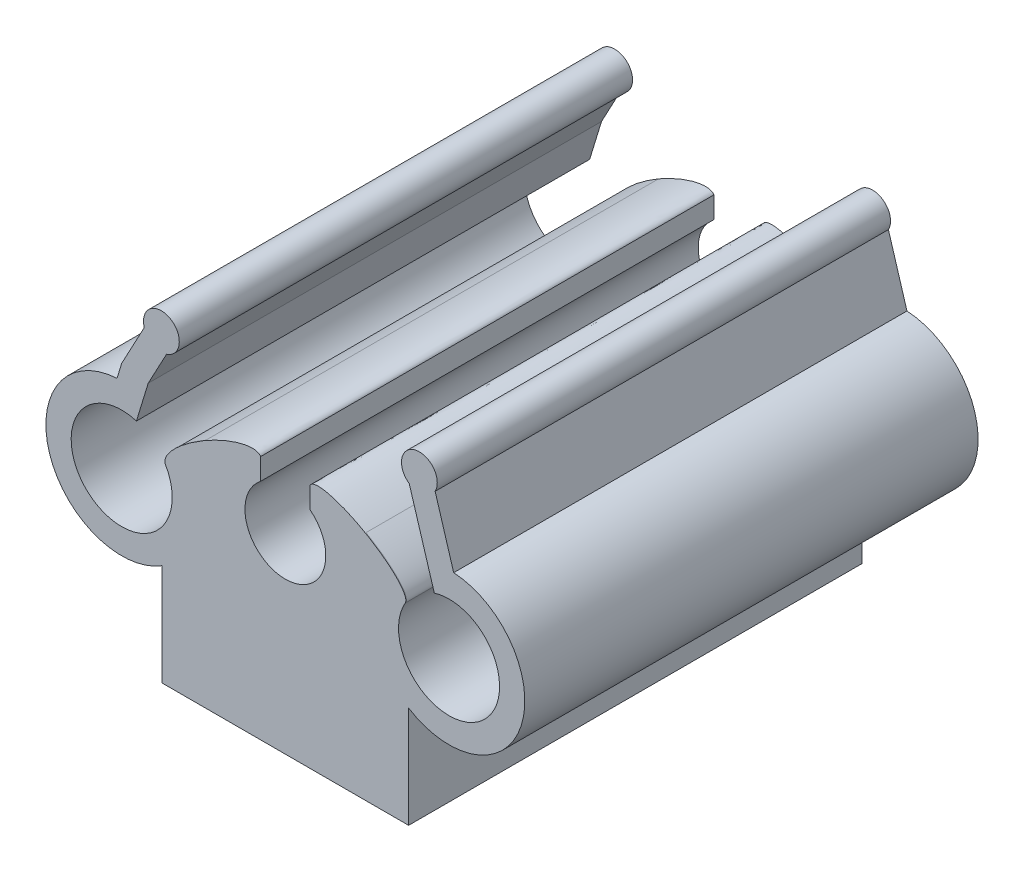
SolidWorks part; units mm, degrees
ref_plane "Ön Düzlem" through (0, 0, 0) normal (0, 0, 1) x (1, 0, 0)
ref_plane "Üst Düzlem" through (0, 0, 0) normal (0, 1, 0) x (1, 0, 0)
ref_plane "Sağ Düzlem" through (0, 0, 0) normal (1, 0, 0) x (0, 0, -1)
sketch "Çizim1" plane through (0, 0, 0) normal (0, 0, 1) x (1, 0, 0)
  line L0 (0, 0) -> (12.2, 0)
  line L1 (12.2, 0) -> (12.2, 4.1689)
  line L3 (0, 4.1689) -> (0, 0)
  line L4 (-2, 12.7) -> (-1.3113, 14.9713)
  line L5 (5.1136, 12.2788) -> (5.1136, 10.9455)
  line L6 (-0.1151, 14.6086) -> (-0.7477, 12.5222)
  line L7 (14.2, 12.7) -> (13.0809, 14.793)
  line L8 (7.0864, 12.2788) -> (7.0864, 10.9455)
  line L9 (11.9786, 14.2036) -> (12.8872, 12.5043)
  line L10 (1.9038, 10.4384) -> (5.1136, 12.2788)
  line L11 (10.2962, 10.4384) -> (7.0864, 12.2788)
  line L12 (10.2962, 10.4384) -> (12.0312, 9.4435)
  line L13 (12.8872, 12.5043) -> (13.4707, 10.5913)
  line L14 (1.9038, 10.4384) -> (0.1688, 9.4435)
  line L15 (-0.7477, 12.5222) -> (-1.3043, 10.6012)
  arc A2 (12.2, 4.1689) -> (14.2, 12.7) centre (14.2, 8.2) ccw
  arc A3 (-2, 12.7) -> (0, 4.1689) centre (-2, 8.2) ccw
  arc A4 (-1.3043, 10.6012) -> (0.1688, 9.4435) centre (-2, 8.2) ccw
  arc A5 (12.0312, 9.4435) -> (13.4707, 10.5913) centre (14.2, 8.2) ccw
  arc A7 (-0.1151, 14.6086) -> (-1.3113, 14.9713) centre (-0.5314, 15.3896) ccw
  arc A8 (13.0809, 14.793) -> (11.9786, 14.2036) centre (12.2343, 15.0509) ccw
  arc A10 (5.1136, 10.9455) -> (7.0864, 10.9455) centre (6.1, 9.5) ccw
  arc A11 (5.1136, 12.2788) -> (4.2001, 11.755) centre (6.1, 9.5) ccw
  arc A12 (7.9999, 11.755) -> (7.0864, 12.2788) centre (6.1, 9.5) ccw
  arc A13 (12.8872, 12.5043) -> (10.2962, 10.4384) centre (14.2, 8.2) ccw
  circle A14 centre (6.1, 9.5) radius 2
  dimension "D3" = 9
  dimension "D4" = 9
  dimension "D9" = 5
  dimension "D10" = 5
  dimension "D13" = 1.77
  dimension "D16" = 1.77
  dimension "D20" = 3.5
  dimension "D11" = 4
  dimension "D1" = 12.2
  dimension "D5" = 2
  dimension "D6" = 2
  dimension "D7" = 8.2
  dimension "D8" = 8.2
  dimension "D17" = 3.7
  dimension "D18" = 3.7
  dimension "D19" = 9.5
extrude "Yükseklik-Ekstrüzyon1" add sketch "Çizim1" along normal blind 22.43 contours A10 L5 L10 L14 A4 L15 L6 A7 L4 A3 L3 L0 L1 A2 L7 A8 L9 L13 A5 L12 L11 L8 region at (6.0884, 6.4179, 0)
sketch "Çizim2" plane through (0, 0, 0) normal (0, 0, -1) x (-1, 0, 0)
  line L0 (-7.0864, 12.2788) -> (-12.0312, 9.4435) construction
  line L1 (-12.0312, 9.4435) -> (-7.0864, 12.2788)
  line L2 (-0.1688, 9.4435) -> (-5.1136, 12.2788) construction
  line L3 (-5.1136, 12.2788) -> (-0.1688, 9.4435)
  ellipse E0 centre (-9.5588, 10.8612) end of major axis (-12.0312, 9.4435) minor radius 0.772 (-7.0864, 12.2788) -> (-12.0312, 9.4435) ccw
  ellipse E1 centre (-2.6412, 10.8612) end of major axis (-0.1688, 9.4435) minor radius 0.77 (-0.1688, 9.4435) -> (-5.1136, 12.2788) ccw
  dimension "D1" = 0.772
extrude "Yükseklik-Ekstrüzyon3" add sketch "Çizim2" against normal blind 22.4
sketch "Çizim3" plane through (0, 0, 0) normal (0, 0, -1) x (-1, 0, 0)
  line L4 (2, 12.7) -> (3.1248, 11.5752)
  line L5 (0, 5.2577) -> (0, 4.1689)
  line L7 (-12.2, 5.2577) -> (-12.2, 4.1689)
  line L8 (-14.2, 12.7) -> (-15.3248, 11.5752)
  arc A4 (2, 12.7) -> (0, 4.1689) centre (2, 8.2) cw
  arc A5 (3.1248, 11.5752) -> (0, 5.2577) centre (2, 8.2) cw
  arc A8 (-14.2, 12.7) -> (-12.2, 4.1689) centre (-14.2, 8.2) ccw
  arc A9 (-15.3248, 11.5752) -> (-12.2, 5.2577) centre (-14.2, 8.2) ccw
extrude "Kes-Ekstrüzyon3" cut sketch "Çizim3" against normal blind 22.5
sketch "Çizim5" plane through (0, 0, 0) normal (0, 0, -1) x (-1, 0, 0)
  line L1 (-7.325, 13.1476) -> (-4.875, 13.1476)
  line L2 (-7.325, 13.1476) -> (-7.325, 11.0809)
  line L3 (-7.325, 11.0809) -> (-4.875, 11.0809)
  line L4 (-4.875, 13.1476) -> (-4.875, 11.0809)
  arc A0 (-7.0864, 11.2398) -> (-5.1136, 11.2398) centre (-6.1, 9.5) ccw construction
  point P7 (-6.1, 7.5)
  dimension "D1" = 1.225
  dimension "D2" = 1.225
extrude "Kes-Ekstrüzyon4" cut sketch "Çizim5" against normal blind 22.5
sketch "Çizim6" plane through (0, 0, 0) normal (0, 0, -1) x (-1, 0, 0)
  line L0 (0, 0) -> (-12.2, 0) construction
  line L1 (-6.1, 0) -> (9.3518, 0)
  line L2 (-6.1, 0) -> (-6.1, 18.2258)
  line L3 (-6.1, 18.2258) -> (9.3518, 18.2258)
  line L4 (9.3518, 0) -> (9.3518, 18.2258)
extrude "Kes-Ekstrüzyon5" cut sketch "Çizim6" against normal blind 22.5
sketch "Çizim7" plane through (0, 0, 0) normal (0, 0, -1) x (-1, 0, 0)
sketch "Çizim9" plane through (0, 0, 22.4) normal (0, 0, 1) x (1, 0, 0)
  line L0 (7.325, 12.142) -> (12.0312, 9.4435) construction
  line L1 (7.325, 12.142) -> (12.0312, 9.4435)
  ellipse E0 centre (9.6781, 10.7928) end of major axis (12.0312, 9.4435) minor radius 0.7711 (12.0312, 9.4435) -> (7.325, 12.142) ccw
extrude "Yükseklik-Ekstrüzyon5" add sketch "Çizim9" along normal blind 0.03
sketch "Çizim10" plane through (0, 0, 22.4) normal (0, 0, 1) x (1, 0, 0)
  line L0 (7.325, 12.4162) -> (7.325, 12.142)
  line L1 (7.325, 12.142) -> (7.325, 12.1362)
  line L2 (7.325, 11.0809) -> (7.325, 12.142) construction
  ellipse E0 centre (9.6781, 10.7928) end of major axis (12.0312, 9.4435) minor radius 0.7711
  ellipse M1 centre (9.6781, 10.7928) end of major axis (12.0312, 9.4435) minor radius 0.7711 (7.325, 12.142) -> (10.0617, 11.4617) cw
  ellipse M2 centre (9.5588, 10.8612) end of major axis (7.0864, 12.2788) minor radius 0.772 (10.0617, 11.4617) -> (7.325, 12.4162) ccw
  line M3 (7.325, 12.4162) -> (7.325, 12.142)
extrude "Kes-Ekstrüzyon7" cut sketch "Çizim10" against normal blind 25 contours M3 M1 M2 region at (8.7367, 12.087, 22.4)
mirror "Aynalama3" about plane through (6.1, 0, 22.5) normal (1, 0, 0) of "Yükseklik-Ekstrüzyon3", "Yükseklik-Ekstrüzyon5", "Kes-Ekstrüzyon4", "Yükseklik-Ekstrüzyon1"
sketch "Çizim11" plane through (0, 0, 0) normal (0, 0, -1) x (-1, 0, 0)
  line L0 (-14.2, 12.7) -> (-14.4295, 11.943)
  line L1 (-12.2, 4.1689) -> (-12.2, 5.0279)
  line L4 (0, 4.1689) -> (0, 5.0279)
  line L5 (2, 12.7) -> (2.2295, 11.943)
  arc A0 (-14.2, 12.7) -> (-12.2, 4.1689) centre (-14.2, 8.2) ccw
  arc A3 (-14.4295, 11.943) -> (-12.2, 5.0279) centre (-14.2, 8.2) ccw
  arc A4 (2, 12.7) -> (0, 4.1689) centre (2, 8.2) cw
  arc A5 (2.2295, 11.943) -> (0, 5.0279) centre (2, 8.2) cw
  dimension "D1" = 7.5
extrude "Kes-Ekstrüzyon8" cut sketch "Çizim11" against normal blind 25
sketch "Çizim13" plane through (0, 0, 22.4) normal (0, 0, 1) x (1, 0, 0)
  line L0 (4.875, 12.142) -> (4.875, 12.4162)
  line L2 (4.875, 12.142) -> (4.875, 12.4162)
  line L3 (4.875, 12.142) -> (4.875, 12.4162)
  line L5 (7.325, 12.142) -> (7.325, 12.4162)
  ellipse E0 centre (9.6781, 10.7928) end of major axis (12.0312, 9.4435) minor radius 0.7711 (7.325, 12.142) -> (10.0617, 11.4617) cw
  ellipse E1 centre (9.5588, 10.8612) end of major axis (12.0312, 9.4435) minor radius 0.772 (7.325, 12.4162) -> (10.0617, 11.4617) cw
  ellipse E2 centre (2.6412, 10.8612) end of major axis (5.1136, 12.2788) minor radius 0.772 (4.875, 12.4162) -> (2.1383, 11.4617) ccw
  ellipse E3 centre (2.5219, 10.7928) end of major axis (0.1688, 9.4435) minor radius 0.7711 (4.875, 12.142) -> (2.1383, 11.4617) ccw
  ellipse E4 centre (2.6412, 10.8612) end of major axis (5.1136, 12.2788) minor radius 0.772 (4.875, 12.4162) -> (2.1383, 11.4617) ccw
  ellipse E5 centre (2.5219, 10.7928) end of major axis (0.1688, 9.4435) minor radius 0.7711 (4.875, 12.142) -> (2.1383, 11.4617) ccw
  ellipse M6 centre (2.6412, 10.8612) end of major axis (5.1136, 12.2788) minor radius 0.772 (4.875, 12.4162) -> (2.1383, 11.4617) ccw
  ellipse M7 centre (2.5219, 10.7928) end of major axis (0.1688, 9.4435) minor radius 0.7711 (2.1383, 11.4617) -> (4.875, 12.142) cw
  line M8 (4.875, 12.142) -> (4.875, 12.4162)
  dimension "D1" = 0
extrude "Kes-Ekstrüzyon9" cut sketch "Çizim13" against normal blind 25 contours E1 L5 E0 | M8 M6 M7 region at (3.4645, 12.1133, 22.4) region at (7.354, 12.2791, 22.4)
sketch "Çizim14" plane through (0, 0, 22.43) normal (0, 0, 1) x (1, 0, 0)
  line L0 (13.4707, 10.5913) -> (11.8044, 16.0544)
  line L1 (11.8044, 16.0544) -> (10.2341, 15.5754)
  line L2 (10.2341, 15.5754) -> (11.7542, 10.5913)
  line L3 (11.7542, 10.5913) -> (13.4707, 10.5913)
extrude "Kes-Ekstrüzyon10" cut sketch "Çizim14" against normal blind 25
sketch "Çizim15" plane through (0, 0, 22.43) normal (0, 0, 1) x (1, 0, 0)
  circle A0 centre (12.7314, 15.3896) radius 0.885
extrude "Yükseklik-Ekstrüzyon7" add sketch "Çizim15" against normal blind 22.43
sketch "Çizim16" plane through (0, 0, 22.43) normal (0, 0, 1) x (1, 0, 0)
  line L0 (11.8652, 15.8552) -> (11.9081, 15.7143)
  line L2 (12.0142, 15.9081) -> (11.9729, 15.9494)
  line L3 (11.9729, 15.9494) -> (11.8622, 15.8658)
  line L4 (11.8622, 15.8658) -> (11.8652, 15.8552)
  arc A0 (12.0142, 15.9081) -> (11.9081, 15.7143) centre (12.7314, 15.3896) ccw
extrude "Kes-Ekstrüzyon12" cut sketch "Çizim16" against normal blind 25
